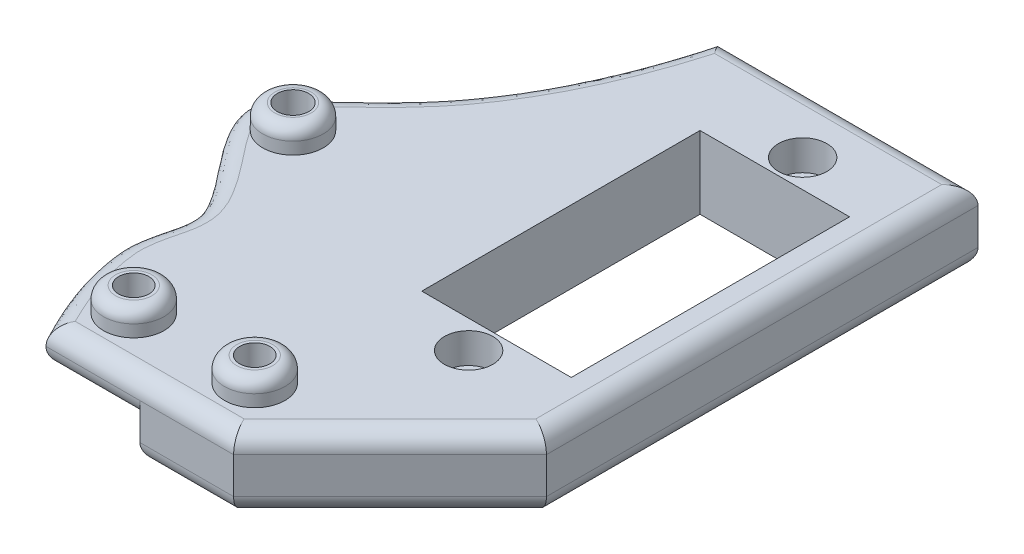
SolidWorks part; units mm, degrees
ref_plane "Front Plane" through (0, 0, 0) normal (0, 0, 1) x (1, 0, 0)
ref_plane "Top Plane" through (0, 0, 0) normal (0, 1, 0) x (1, 0, 0)
ref_plane "Right Plane" through (0, 0, 0) normal (1, 0, 0) x (0, 0, -1)
ref_plane "Plane1" through (0, -3, 0) normal (0, -1, 0) x (1, 0, 0)
sketch "Sketch1" plane through (0, -3, 0) normal (0, -1, 0) x (1, 0, 0)
  line L0 (-0.7263, -25.4372) -> (20.68, -25.4372)
  line L1 (20.68, -25.4372) -> (20.68, 10.2357)
  line L2 (20.68, 10.2357) -> (7.7534, 23.1623)
  line L3 (7.7534, 23.1623) -> (-7.7534, 23.1623)
  spline S0 degree 3 poles (-7.7534, 23.1623) (-9.1828, 20.4296) (-10.4544, 17.4691) (-10.711, 14.3958) (-10.8218, 13.0681) (-10.4743, 11.7305) (-10.1479, 10.4388) (-10.0047, 9.8721) (-9.9188, 9.2706) (-9.9988, 8.6916) (-10.0797, 8.1064) (-10.3255, 7.5449) (-10.6147, 7.0297) (-11.6442, 5.1954) (-13.1223, 3.6506) (-14.3122, 1.9161) (-14.7216, 1.3194) (-15.112, 0.6986) (-15.3831, 0.0277) (-15.5055, -0.2754) (-15.6035, -0.5936) (-15.6421, -0.9182) (-15.6743, -1.1885) (-15.6621, -1.4683) (-15.6027, -1.7339) (-15.5433, -1.999) (-15.4374, -2.2553) (-15.3052, -2.4926) (-14.963, -3.1068) (-14.4604, -3.6242) (-13.9556, -4.1136) (-11.6768, -6.323) (-9.2451, -8.4256) (-7.3498, -10.9716) (-4.86, -14.316) (-3.0341, -18.1835) (-1.7146, -22.1386) (-1.3514, -23.2275) (-1.0234, -24.3285) (-0.7263, -25.4372) knots 0 0 0 0 0.009252 0.009252 0.009252 0.013232 0.013232 0.013232 0.014992 0.014992 0.014992 0.016768 0.016768 0.016768 0.023058 0.023058 0.023058 0.025228 0.025228 0.025228 0.026207 0.026207 0.026207 0.027025 0.027025 0.027025 0.027838 0.027838 0.027838 0.02996 0.02996 0.02996 0.039493 0.039493 0.039493 0.052103 0.052103 0.052103 0.055539 0.055539 0.055539 0.055539
extrude "Boss-Extrude1" add sketch "Sketch1" against normal blind 3
sketch "Sketch2" plane through (0, 0, 0) normal (0, 1, 0) x (-1, 0, 0)
  line L0 (-17.68, -17.82) -> (-5.32, -17.82)
  line L1 (-5.32, -17.82) -> (-5.32, 5.18)
  line L2 (-5.32, 5.18) -> (-17.68, 5.18)
  line L3 (-17.68, 5.18) -> (-17.68, -17.82)
extrude "Cut-Extrude1" cut sketch "Sketch2" against normal through all
hole_wizard "Ø2.6 (2.6) Diameter Hole1" positions "Sketch4" profile "Sketch3" hole size "Ø2.6" standard "ANSI Metric"
sketch "Sketch4" plane through (0, 0, 0) normal (0, 1, 0) x (1, 0, 0)
  point P0 (-11.5, 1)
sketch "Sketch3" plane through (-11.5, 0, -1) normal (1, 0, 0) x (0, 0, 1)
  line L0 (0, 0) -> (0, 3)
  line L1 (0, 3) -> (1.3, 3)
  line L2 (1.3, 3) -> (1.3, 0)
  line L5 (1.3, 0) -> (0, 0)
  line L11 (0, -6.35) -> (0, 107.95) construction
  dimension "Thru Hole Dia." = 2.6
  dimension "Thru Hole Depth" = 3
hole_wizard "Ø2.0 (2) Diameter Hole1" positions "Sketch6" profile "Sketch5" hole size "Ø2.0" standard "ANSI Metric"
sketch "Sketch6" plane through (0, 0, 0) normal (0, 1, 0) x (1, 0, 0)
  point P0 (-5, -18.6623)
  point P1 (5, -18.6623)
sketch "Sketch5" plane through (-5, 0, 18.6623) normal (1, 0, 0) x (0, 0, 1)
  line L0 (0, 0) -> (0, 3)
  line L1 (0, 3) -> (1, 3)
  line L2 (1, 3) -> (1, 0)
  line L5 (1, 0) -> (0, 0)
  line L11 (0, -6.35) -> (0, 107.95) construction
  dimension "Thru Hole Dia." = 2
  dimension "Thru Hole Depth" = 3
hole_wizard "Ø2.2 (2.2) Diameter Hole1" positions "Sketch8" profile "Sketch7" hole size "Ø2.2" standard "ANSI Metric"
sketch "Sketch8" plane through (0, 0, 0) normal (0, 1, 0) x (1, 0, 0)
  point P0 (11.5, -7.485)
  point P1 (11.5, 20.125)
sketch "Sketch7" plane through (11.5, 0, 7.485) normal (1, 0, 0) x (0, 0, 1)
  line L0 (0, 0) -> (0, 3)
  line L1 (0, 3) -> (1.1, 3)
  line L2 (1.1, 3) -> (1.1, 0)
  line L5 (1.1, 0) -> (0, 0)
  line L11 (0, -6.35) -> (0, 107.95) construction
  dimension "Thru Hole Dia." = 2.2
  dimension "Thru Hole Depth" = 3
sketch "Sketch9" plane through (0, -3, 0) normal (0, -1, 0) x (1, 0, 0)
  line L0 (0, 23.1623) -> (0, -25.4372)
  line L4 (-0.7263, -25.4372) -> (20.68, -25.4372)
  line L5 (20.68, -25.4372) -> (20.68, 10.2357)
  line L6 (20.68, 10.2357) -> (7.7534, 23.1623)
  line L7 (7.7534, 23.1623) -> (-7.7534, 23.1623)
  line L8 (0, -25.4372) -> (20.68, -25.4372)
  line L9 (20.68, -25.4372) -> (20.68, 10.2357)
  line L10 (20.68, 10.2357) -> (7.7534, 23.1623)
  line L11 (7.7534, 23.1623) -> (0, 23.1623)
  spline S1 degree 3 poles (-998.1987, -114.7051) (137.7071, 71.3604) (-7.6733, 50.7884) (-10.711, 14.3958) (-10.8218, 13.0681) (-10.4743, 11.7305) (-10.1479, 10.4388) (-10.0047, 9.8721) (-9.9188, 9.2706) (-9.9988, 8.6916) (-10.0797, 8.1064) (-10.3255, 7.5449) (-10.6147, 7.0297) (-11.6442, 5.1954) (-13.1223, 3.6506) (-14.3122, 1.9161) (-14.7216, 1.3194) (-15.112, 0.6986) (-15.3831, 0.0277) (-15.5055, -0.2754) (-15.6035, -0.5936) (-15.6421, -0.9182) (-15.6743, -1.1885) (-15.6621, -1.4683) (-15.6027, -1.7339) (-15.5433, -1.999) (-15.4374, -2.2553) (-15.3052, -2.4926) (-14.963, -3.1068) (-14.4604, -3.6242) (-13.9556, -4.1136) (-11.6768, -6.323) (-9.2451, -8.4256) (-7.3498, -10.9716) (-4.86, -14.316) (-3.0341, -18.1835) (-1.7146, -22.1386) (20.5839, -88.9787) (-90.1182, -201.9165) (688.3502, 699.2494) knots -0.100306 -0.100306 -0.100306 -0.100306 0.009252 0.009252 0.009252 0.013232 0.013232 0.013232 0.014992 0.014992 0.014992 0.016768 0.016768 0.016768 0.023058 0.023058 0.023058 0.025228 0.025228 0.025228 0.026207 0.026207 0.026207 0.027025 0.027025 0.027025 0.027838 0.027838 0.027838 0.02996 0.02996 0.02996 0.039493 0.039493 0.039493 0.052103 0.052103 0.052103 0.263052 0.263052 0.263052 0.263052 only from (-7.7534, 23.1623) to (-0.7263, -25.4372)
  dimension "D1" = 0
extrude "Boss-Extrude2" add sketch "Sketch9" along normal blind 3
sketch "Sketch11" plane through (0, 0, 0) normal (0, 1, 0) x (1, 0, 0)
  line L4 (5.32, 17.82) -> (5.32, -5.18)
  line L5 (5.32, -5.18) -> (17.68, -5.18)
  line L6 (17.68, -5.18) -> (17.68, 17.82)
  line L7 (17.68, 17.82) -> (5.32, 17.82)
  line L8 (5.32, 17.82) -> (5.32, -5.18)
  line L9 (5.32, -5.18) -> (17.68, -5.18)
  line L10 (17.68, -5.18) -> (17.68, 17.82)
  line L11 (17.68, 17.82) -> (5.32, 17.82)
  dimension "D1" = 0
extrude "Cut-Extrude2" cut sketch "Sketch11" against normal through all
sketch "Sketch12" plane through (0, 0, 0) normal (0, 1, 0) x (1, 0, 0)
  circle A0 centre (5, -18.6623) radius 1 construction
  circle A1 centre (5, -18.6623) radius 1
  circle A2 centre (11.5, -7.485) radius 1.1 construction
  circle A3 centre (11.5, -7.485) radius 1.1
  circle A4 centre (11.5, 20.125) radius 1.1 construction
  circle A5 centre (11.5, 20.125) radius 1.1
extrude "Cut-Extrude3" cut sketch "Sketch12" against normal through all
sketch "Sketch13" plane through (0, 0, 0) normal (0, 1, 0) x (1, 0, 0)
  circle A4 centre (11.5, -7.485) radius 2
  circle A5 centre (11.5, 20.125) radius 2
  dimension "D1" = 4
  dimension "D2" = 4
extrude "Cut-Extrude4" cut sketch "Sketch13" against normal blind 2.5
fillet "Fillet3" radius 1.5 12 edges at (-3.8767, -3, 23.1623) (3.8767, -6, 23.1623) (0, -6, -1.1374) (10.34, -6, -25.4372) (20.68, -6, -7.6007) (14.2167, -6, 16.699) (9.9768, 0, -25.4372) (0, 0, 23.1623) (14.2167, 0, 16.699) (20.68, 0, -7.6007)
sketch "Sketch14" plane through (0, 0, 0) normal (0, 1, 0) x (1, 0, 0)
  line L0 (-4, -18.6623) -> (-6, -18.6623) construction
  circle A0 centre (5, -18.6623) radius 1.25
  circle A1 centre (-5, -18.6623) radius 1 construction
  circle A2 centre (-5, -18.6623) radius 1.25
  dimension "D1" = 2.5
  dimension "D2" = 2.5
extrude "Cut-Extrude5" cut sketch "Sketch14" against normal through all
sketch "Sketch15" plane through (0, 0, 0) normal (0, 1, 0) x (1, 0, 0)
  circle A0 centre (5, -18.6623) radius 2.5
  circle A1 centre (5, -18.6623) radius 1.25 construction
  circle A2 centre (5, -18.6623) radius 1.25
  circle A3 centre (-5, -18.6623) radius 1.25 construction
  circle A4 centre (-5, -18.6623) radius 1.25
  circle A5 centre (-5, -18.6623) radius 2.5
  circle A6 centre (-11.5, 1) radius 1.3 construction
  circle A7 centre (-11.5, 1) radius 1.3
  circle A8 centre (-11.5, 1) radius 2.5
  dimension "D1" = 5
  dimension "D2" = 5
  dimension "D3" = 5
extrude "Boss-Extrude3" add sketch "Sketch15" along normal blind 2
fillet "Fillet4" radius 1 3 edges at (-11.5, 2, 1.5) (-5, 2, 21.1623) (5, 2, 21.1623)
